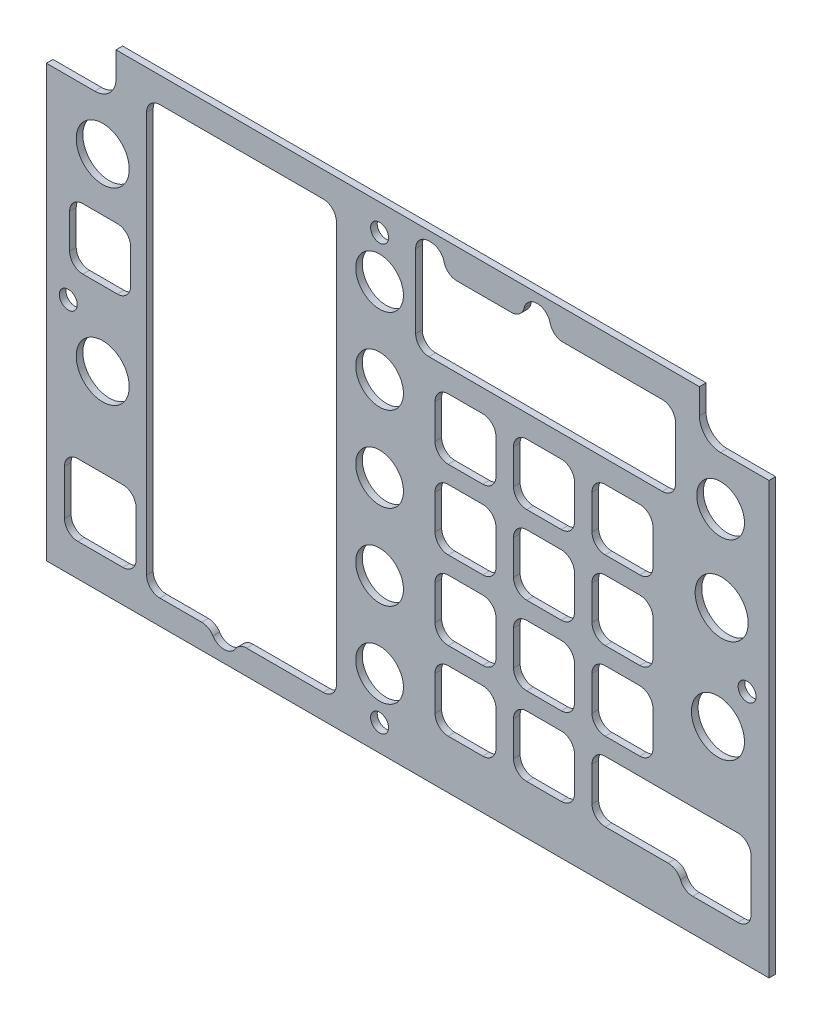
SolidWorks part; units mm, degrees
material "ABS PC"
ref_plane "Front Plane" through (0, 0, 0) normal (0, 0, 1) x (1, 0, 0)
ref_plane "Top Plane" through (0, 0, 0) normal (0, 1, 0) x (1, 0, 0)
ref_plane "Right Plane" through (0, 0, 0) normal (1, 0, 0) x (0, 0, -1)
sketch "Sketch1" plane through (0, 0, 0) normal (0, 0, 1) x (1, 0, 0)
  line L8 (58.2068, 169.534) -> (58.2068, 175.5665)
  line L9 (58.2068, 175.5665) -> (-81.4932, 175.5665)
  line L10 (-81.4932, 175.5665) -> (-81.4932, 169.534)
  line L11 (-86.5732, 164.454) -> (-98.162, 164.454)
  line L12 (-98.162, 164.454) -> (-98.162, 61.2665)
  line L13 (-98.162, 61.2665) -> (74.8755, 61.2665)
  line L14 (74.8755, 61.2665) -> (74.8755, 164.454)
  line L15 (74.8755, 164.454) -> (63.2868, 164.454)
  line L16 (58.2068, 169.534) -> (58.2068, 175.5665)
  line L17 (58.2068, 175.5665) -> (-81.4932, 175.5665)
  line L18 (-81.4932, 175.5665) -> (-81.4932, 169.534)
  line L19 (-86.5732, 164.454) -> (-98.162, 164.454)
  line L20 (-98.162, 164.454) -> (-98.162, 61.2665)
  line L21 (-98.162, 61.2665) -> (74.8755, 61.2665)
  line L22 (74.8755, 61.2665) -> (74.8755, 164.454)
  line L23 (74.8755, 164.454) -> (63.2868, 164.454)
  arc A2 (58.2068, 169.534) -> (63.2868, 164.454) centre (63.2868, 169.534) ccw
  arc A3 (-86.5732, 164.454) -> (-81.4932, 169.534) centre (-86.5732, 169.534) ccw
  arc A4 (58.2068, 169.534) -> (63.2868, 164.454) centre (63.2868, 169.534) ccw
  arc A5 (-86.5732, 164.454) -> (-81.4932, 169.534) centre (-86.5732, 169.534) ccw
  dimension "D1" = 0
extrude "Boss-Extrude1" add sketch "Sketch1" along normal blind 1.5875
sketch "Sketch2" plane through (0, 0, 1.5875) normal (0, 0, 1) x (1, 0, 0)
  line L0 (32.4893, 129.402) -> (47.0943, 129.402)
  line L1 (32.4893, 144.007) -> (32.4893, 129.402)
  line L2 (47.0943, 144.007) -> (32.4893, 144.007)
  line L3 (47.0943, 129.402) -> (47.0943, 144.007)
  line L4 (69.005, 84.6495) -> (55.005, 70.6495) construction
  line L5 (-78.2558, 84.633) -> (-92.2558, 70.633) construction
  line L6 (70.5775, 69.077) -> (53.4325, 69.077)
  line L7 (70.5775, 69.077) -> (70.5775, 86.222)
  line L8 (70.5775, 86.222) -> (53.4325, 86.222)
  line L9 (53.4325, 69.077) -> (53.4325, 86.222)
  line L10 (70.5775, 69.077) -> (53.4325, 86.222) construction
  line L11 (70.5775, 86.222) -> (53.4325, 69.077) construction
  line L12 (13.6933, 129.402) -> (28.2983, 129.402)
  line L13 (13.6933, 144.007) -> (13.6933, 129.402)
  line L14 (28.2983, 144.007) -> (13.6933, 144.007)
  line L15 (28.2983, 129.402) -> (28.2983, 144.007)
  line L16 (9.5023, 144.007) -> (-5.1027, 144.007)
  line L17 (9.5023, 129.402) -> (9.5023, 144.007)
  line L18 (-5.1027, 129.402) -> (9.5023, 129.402)
  line L19 (-5.1027, 144.007) -> (-5.1027, 129.402)
  line L20 (32.4893, 110.606) -> (32.4893, 129.402) construction
  line L22 (49.8768, 158.9295) -> (-7.1232, 158.9295) construction
  line L23 (52.4918, 168.4545) -> (-9.7382, 168.4545)
  line L24 (52.4918, 168.4545) -> (52.4918, 149.4045)
  line L25 (52.4918, 149.4045) -> (-9.7382, 149.4045)
  line L26 (32.4893, 73.014) -> (47.0943, 73.014)
  line L27 (32.4893, 87.619) -> (32.4893, 73.014)
  line L28 (47.0943, 87.619) -> (32.4893, 87.619)
  line L29 (47.0943, 73.014) -> (47.0943, 87.619)
  line L30 (32.4893, 73.014) -> (47.0943, 73.014)
  line L31 (32.4893, 87.619) -> (32.4893, 73.014)
  line L32 (47.0943, 87.619) -> (32.4893, 87.619)
  line L33 (47.0943, 73.014) -> (47.0943, 87.619)
  line L34 (32.4893, 91.81) -> (47.0943, 91.81)
  line L35 (32.4893, 106.415) -> (32.4893, 91.81)
  line L36 (47.0943, 106.415) -> (32.4893, 106.415)
  line L37 (47.0943, 91.81) -> (47.0943, 106.415)
  line L38 (32.4893, 91.81) -> (47.0943, 91.81)
  line L39 (32.4893, 106.415) -> (32.4893, 91.81)
  line L40 (47.0943, 106.415) -> (32.4893, 106.415)
  line L41 (47.0943, 91.81) -> (47.0943, 106.415)
  line L42 (32.4893, 110.606) -> (47.0943, 110.606)
  line L43 (32.4893, 125.211) -> (32.4893, 110.606)
  line L44 (47.0943, 125.211) -> (32.4893, 125.211)
  line L45 (47.0943, 110.606) -> (47.0943, 125.211)
  line L46 (32.4893, 110.606) -> (47.0943, 110.606)
  line L47 (32.4893, 125.211) -> (32.4893, 110.606)
  line L48 (47.0943, 125.211) -> (32.4893, 125.211)
  line L49 (47.0943, 110.606) -> (47.0943, 125.211)
  line L50 (-9.7382, 168.4545) -> (-9.7382, 149.4045)
  line L51 (13.6933, 73.014) -> (28.2983, 73.014)
  line L52 (13.6933, 87.619) -> (13.6933, 73.014)
  line L53 (28.2983, 87.619) -> (13.6933, 87.619)
  line L54 (28.2983, 73.014) -> (28.2983, 87.619)
  line L55 (13.6933, 73.014) -> (28.2983, 73.014)
  line L56 (13.6933, 87.619) -> (13.6933, 73.014)
  line L57 (28.2983, 87.619) -> (13.6933, 87.619)
  line L58 (28.2983, 73.014) -> (28.2983, 87.619)
  line L59 (13.6933, 91.81) -> (28.2983, 91.81)
  line L60 (13.6933, 106.415) -> (13.6933, 91.81)
  line L61 (28.2983, 106.415) -> (13.6933, 106.415)
  line L62 (-93.8283, 69.0605) -> (-76.6833, 69.0605)
  line L63 (-93.8283, 69.0605) -> (-93.8283, 86.2055)
  line L64 (-93.8283, 86.2055) -> (-76.6833, 86.2055)
  line L65 (-76.6833, 69.0605) -> (-76.6833, 86.2055)
  line L66 (-93.8283, 69.0605) -> (-76.6833, 86.2055) construction
  line L67 (-93.8283, 86.2055) -> (-76.6833, 69.0605) construction
  line L94 (28.2983, 91.81) -> (28.2983, 106.415)
  line L95 (13.6933, 91.81) -> (28.2983, 91.81)
  line L96 (13.6933, 106.415) -> (13.6933, 91.81)
  line L97 (28.2983, 106.415) -> (13.6933, 106.415)
  line L98 (28.2983, 91.81) -> (28.2983, 106.415)
  line L99 (13.6933, 110.606) -> (28.2983, 110.606)
  line L100 (13.6933, 125.211) -> (13.6933, 110.606)
  line L101 (28.2983, 125.211) -> (13.6933, 125.211)
  line L102 (28.2983, 110.606) -> (28.2983, 125.211)
  line L103 (13.6933, 110.606) -> (28.2983, 110.606)
  line L104 (13.6933, 125.211) -> (13.6933, 110.606)
  line L105 (28.2983, 125.211) -> (13.6933, 125.211)
  line L106 (28.2983, 110.606) -> (28.2983, 125.211)
  line L107 (9.5023, 125.211) -> (-5.1027, 125.211)
  line L108 (9.5023, 110.606) -> (9.5023, 125.211)
  line L109 (-5.1027, 110.606) -> (9.5023, 110.606)
  line L110 (-5.1027, 125.211) -> (-5.1027, 110.606)
  line L111 (9.5023, 125.211) -> (-5.1027, 125.211)
  line L112 (9.5023, 110.606) -> (9.5023, 125.211)
  line L113 (-5.1027, 110.606) -> (9.5023, 110.606)
  line L114 (-5.1027, 125.211) -> (-5.1027, 110.606)
  line L115 (-5.1027, 91.81) -> (9.5023, 91.81)
  line L116 (-5.1027, 106.415) -> (-5.1027, 91.81)
  line L117 (9.5023, 106.415) -> (-5.1027, 106.415)
  line L118 (9.5023, 91.81) -> (9.5023, 106.415)
  line L119 (-5.1027, 91.81) -> (9.5023, 91.81)
  line L120 (-5.1027, 106.415) -> (-5.1027, 91.81)
  line L121 (9.5023, 106.415) -> (-5.1027, 106.415)
  line L122 (9.5023, 91.81) -> (9.5023, 106.415)
  line L123 (-5.1027, 73.014) -> (9.5023, 73.014)
  line L124 (-5.1027, 87.619) -> (-5.1027, 73.014)
  line L125 (9.5023, 87.619) -> (-5.1027, 87.619)
  line L126 (9.5023, 73.014) -> (9.5023, 87.619)
  line L127 (-5.1027, 73.014) -> (9.5023, 73.014)
  line L128 (-5.1027, 87.619) -> (-5.1027, 73.014)
  line L129 (9.5023, 87.619) -> (-5.1027, 87.619)
  line L130 (9.5023, 73.014) -> (9.5023, 87.619)
  line L131 (-78.0007, 139.689) -> (-92.6057, 139.689)
  line L132 (-78.0007, 125.084) -> (-78.0007, 139.689)
  line L133 (-92.6057, 125.084) -> (-78.0007, 125.084)
  line L134 (-92.6057, 139.689) -> (-92.6057, 125.084)
  line L135 (-78.0007, 139.689) -> (-92.6057, 139.689)
  line L136 (-78.0007, 125.084) -> (-78.0007, 139.689)
  line L137 (-92.6057, 125.084) -> (-78.0007, 125.084)
  line L138 (-92.6057, 139.689) -> (-92.6057, 125.084)
  line L139 (-74.1732, 67.1295) -> (-28.7112, 67.1295)
  line L140 (-74.1732, 169.4495) -> (-74.1732, 67.1295)
  line L141 (-28.7112, 169.4495) -> (-74.1732, 169.4495)
  line L142 (-28.7112, 67.1295) -> (-28.7112, 169.4495)
  line L143 (-74.1732, 67.1295) -> (-28.7112, 67.1295)
  line L144 (-74.1732, 169.4495) -> (-74.1732, 67.1295)
  line L145 (-28.7112, 169.4495) -> (-74.1732, 169.4495)
  line L146 (-28.7112, 67.1295) -> (-28.7112, 169.4495)
  circle A0 centre (-84.6682, 152.389) radius 6.35
  circle A1 centre (-84.6682, 107.304) radius 6.35
  circle A2 centre (63.5408, 132.3865) radius 6.35
  circle A3 centre (62.6518, 107.304) radius 6.35
  circle A10 centre (-18.3742, 77.7765) radius 5.715 construction
  circle A11 centre (-18.3742, 98.0965) radius 5.715 construction
  circle A12 centre (-18.3742, 118.4165) radius 5.715 construction
  circle A13 centre (-18.3742, 138.7365) radius 5.715 construction
  circle A14 centre (-18.3742, 159.0565) radius 5.715 construction
  circle A15 centre (-18.3742, 77.7765) radius 5.715
  circle A16 centre (-18.3742, 98.0965) radius 5.715
  circle A17 centre (-18.3742, 118.4165) radius 5.715
  circle A18 centre (-18.3742, 138.7365) radius 5.715
  circle A19 centre (-18.3742, 159.0565) radius 5.715
  circle A20 centre (63.2868, 152.7065) radius 5.715 construction
  circle A21 centre (63.2868, 152.7065) radius 5.715
  point P94 (-85.2558, 77.633)
  point P97 (-85.2558, 77.633)
  point P98 (62.005, 77.6495)
  point P99 (62.005, 77.6495)
  point P104 (21.3768, 158.9295)
  point P109 (21.3768, 168.4545)
  point P113 (52.4918, 158.9295)
  dimension "D1" = 12.7
  dimension "D16" = 18.796
  dimension "D17" = 19.05
  dimension "D18" = 62.23
  dimension "D2" = 17.145
  dimension "D3" = 0
  dimension "D4" = 0
  dimension "D5" = 0
  dimension "D6" = 2
  dimension "D7" = 0
  dimension "D8" = 0
  dimension "D9" = 0
  dimension "D10" = 0
  dimension "D11" = 0
  dimension "D12" = 0
  dimension "D13" = 0
  dimension "D14" = 0
extrude "Cut-Extrude1" cut sketch "Sketch2" against normal through all
hole_wizard "#6 Clearance Hole2" positions "Sketch5" profile "Sketch6" hole size "#6" standard "ANSI Inch" end condition through all
sketch "Sketch5" plane through (-11.6432, -6.6627, -3.175) normal (0, 0, -1) x (-1, 0, 0)
  point P0 (-81.28, 124.6982)
  point P3 (6.731, 175.8792)
  point P6 (81.28, 124.6982)
  point P9 (6.731, 74.2792)
sketch "Sketch6" plane through (69.6368, 118.0355, -3.175) normal (1, 0, 0) x (0, 1, 0)
  line L0 (0, 0) -> (0, 4.7625)
  line L1 (0, 4.7625) -> (2.1526, 4.7625)
  line L2 (2.1526, 4.7625) -> (2.1526, 0)
  line L3 (2.1526, 0) -> (0, 0)
  line L4 (0, -6.35) -> (0, 107.95) construction
  dimension "Thru Hole Dia." = 4.3053
  dimension "Thru Hole Depth" = 4.7625
sketch "Sketch7" plane through (0, 0, 1.5875) normal (0, 0, 1) x (1, 0, 0)
  line L0 (62.005, 85.1738) -> (62.005, 70.1738) construction
  line L1 (54.505, 85.1738) -> (69.505, 85.1738)
  line L2 (54.505, 85.1738) -> (54.505, 70.1738)
  line L3 (54.505, 70.1738) -> (69.505, 70.1738)
  line L4 (69.505, 85.1738) -> (69.505, 70.1738)
  line L5 (-77.7558, 70.1165) -> (-92.7558, 70.1165)
  line L6 (-77.7558, 70.1165) -> (-77.7558, 85.1165)
  line L7 (-77.7558, 85.1165) -> (-92.7558, 85.1165)
  line L8 (-92.7558, 70.1165) -> (-92.7558, 85.1165)
  line L9 (-85.2558, 85.1165) -> (-85.2558, 70.1165) construction
  point P10 (62.005, 77.6738)
  point P13 (-85.2558, 77.6165)
  dimension "D1" = 15
extrude "Cut-Extrude2" [suppressed] cut sketch "Sketch7" against normal up to next
hole_wizard "1/4 (0.25) Diameter Hole1" positions "Sketch8" profile "Sketch9" hole size "1/4" standard "ANSI Inch" end condition through all
sketch "Sketch8" plane through (0, 0, 0) normal (0, 0, -1) x (-1, 0, 0)
  point P0 (55.5832, 67.3415)
  point P2 (-49.8268, 81.9465)
  point P4 (-19.3468, 170.2115)
  point P6 (6.0532, 170.2115)
sketch "Sketch9" plane through (-55.5832, 67.3415, 0) normal (1, 0, 0) x (0, 1, 0)
  line L0 (0, 0) -> (0, 1.5875)
  line L1 (0, 1.5875) -> (3.175, 1.5875)
  line L2 (3.175, 1.5875) -> (3.175, 0)
  line L5 (3.175, 0) -> (0, 0)
  line L11 (0, -6.35) -> (0, 107.95) construction
  dimension "Thru Hole Dia." = 6.35
  dimension "Thru Hole Depth" = 1.5875
sketch "Sketch10" plane through (0, 0, 0) normal (0, 0, -1) x (-1, 0, 0)
  line L0 (9.7382, 168.4545) -> (9.7382, 173.3865)
  line L1 (9.7382, 168.4545) -> (9.7382, 149.4045) construction
  line L2 (9.7382, 168.4545) -> (8.6978, 168.4545)
  line L3 (6.0532, 173.3865) -> (9.7382, 173.3865)
  line L4 (-47.0943, 87.619) -> (-32.4893, 87.619) construction
  line L6 (-47.0943, 87.619) -> (-47.0943, 73.014)
  line L7 (-47.0943, 73.014) -> (-53.4325, 73.014)
  line L8 (-53.4325, 86.222) -> (-53.4325, 73.014)
  line L9 (-47.0943, 83.5633) -> (-47.0943, 87.619) construction
  line L10 (-53.4325, 86.222) -> (-53.4325, 69.077) construction
  line L11 (-32.4893, 73.014) -> (-47.0943, 73.014) construction
  line L12 (-70.5775, 86.222) -> (-53.4325, 86.222) construction
  line L13 (-47.0943, 87.619) -> (-70.5775, 87.619)
  line L15 (-53.4325, 86.222) -> (-70.5775, 86.222)
  line L16 (-70.5775, 87.619) -> (-70.5775, 86.222)
  line L17 (-70.5775, 69.077) -> (-70.5775, 86.222) construction
  arc A0 (8.6978, 168.4545) -> (3.4087, 168.4545) centre (6.0532, 170.2115) ccw construction
  arc A1 (8.6978, 168.4545) -> (6.0532, 173.3865) centre (6.0532, 170.2115) ccw
  point P25 (-47.6309, 87.619)
extrude "Cut-Extrude3" cut sketch "Sketch10" against normal through all
fillet "Fillet1" radius 3.175 70 edges at (-78.0007, 139.689, 0.7937) (-78.0007, 125.084, 0.7937) (-92.6057, 125.084, 0.7937) (-92.6057, 139.689, 0.7937) (-74.1732, 169.4495, 0.7937) (-28.7112, 169.4495, 0.7937) (-28.7112, 67.1295, 0.7937) (-52.4153, 67.1295, 0.7937) (-58.7512, 67.1295, 0.7937) (-74.1732, 67.1295, 0.7937) (-93.8283, 69.0605, 0.7937) (-93.8283, 86.2055, 0.7937) (-76.6833, 86.2055, 0.7937) (-76.6833, 69.0605, 0.7937) (32.4893, 73.014, 0.7937) (70.5775, 87.619, 0.7937) (70.5775, 69.077, 0.7937) (53.4325, 69.077, 0.7937) (32.4893, 87.619, 0.7937) (13.6933, 73.014, 0.7937) (28.2983, 87.619, 0.7937) (28.2983, 73.014, 0.7937) (13.6933, 87.619, 0.7937) (-5.1027, 73.014, 0.7937) (9.5023, 87.619, 0.7937) (9.5023, 73.014, 0.7937) (-5.1027, 87.619, 0.7937) (-5.1027, 91.81, 0.7937) (-5.1027, 106.415, 0.7937) (9.5023, 91.81, 0.7937) (9.5023, 106.415, 0.7937) (13.6933, 91.81, 0.7937) (13.6933, 106.415, 0.7937) (28.2983, 91.81, 0.7937) (28.2983, 106.415, 0.7937) (32.4893, 91.81, 0.7937) (47.0943, 106.415, 0.7937) (47.0943, 91.81, 0.7937) (32.4893, 106.415, 0.7937) (32.4893, 110.606, 0.7937) (47.0943, 125.211, 0.7937) (47.0943, 110.606, 0.7937) (32.4893, 125.211, 0.7937) (13.6933, 110.606, 0.7937) (28.2983, 125.211, 0.7937) (28.2983, 110.606, 0.7937) (13.6933, 125.211, 0.7937) (9.5023, 110.606, 0.7937) (-5.1027, 110.606, 0.7937) (-5.1027, 125.211, 0.7937) (9.5023, 125.211, 0.7937) (9.5023, 129.402, 0.7937) (-5.1027, 129.402, 0.7937) (-5.1027, 144.007, 0.7937) (9.5023, 144.007, 0.7937) (13.6933, 129.402, 0.7937) (13.6933, 144.007, 0.7937) (28.2983, 129.402, 0.7937) (28.2983, 144.007, 0.7937) (32.4893, 129.402, 0.7937) (47.0943, 144.007, 0.7937) (47.0943, 129.402, 0.7937) (32.4893, 144.007, 0.7937) (52.4918, 168.4545, 0.7937) (52.4918, 149.4045, 0.7937) (-9.7382, 149.4045, 0.7937) (-9.7382, 173.3865, 0.7937) (-3.4087, 168.4545, 0.7937) (16.7022, 168.4545, 0.7937) (21.9913, 168.4545, 0.7937)
fillet "Fillet2" radius 3.175 1 edges at (53.4325, 73.014, 0.7937)
